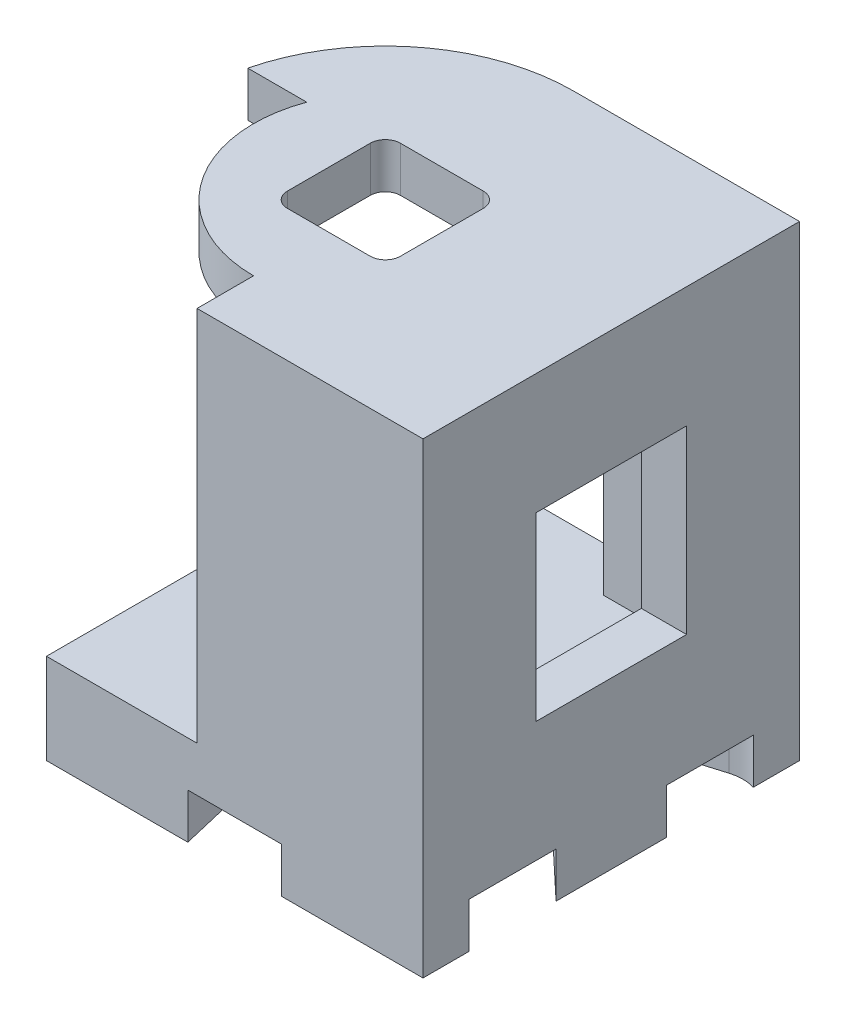
SolidWorks part; units mm, degrees
material "PBT General Purpose"
ref_plane "Front Plane" through (0, 0, 0) normal (0, 0, 1) x (1, 0, 0)
ref_plane "Top Plane" through (0, 0, 0) normal (0, 1, 0) x (1, 0, 0)
ref_plane "Right Plane" through (0, 0, 0) normal (1, 0, 0) x (0, 0, -1)
sketch "Sketch1" plane through (0, 0, 0) normal (0, 1, 0) x (1, 0, 0)
  line L1 (3.75, -3.75) -> (-3.75, -3.75)
  line L2 (3.75, -3.75) -> (3.75, 3.75)
  line L3 (3.75, 3.75) -> (-3.75, 3.75)
  line L4 (-3.75, -3.75) -> (-3.75, 3.75)
  line L5 (3.75, -3.75) -> (-3.75, 3.75) construction
  line L6 (3.75, 3.75) -> (-3.75, -3.75) construction
  line L7 (-15, -12.5) -> (15, -12.5)
  line L8 (-15, -12.5) -> (-15, 12.5)
  line L9 (-15, 12.5) -> (15, 12.5)
  line L10 (15, -12.5) -> (15, 12.5)
  line L11 (-15, -12.5) -> (15, 12.5) construction
  line L12 (-15, 12.5) -> (15, -12.5) construction
  point P0 (0, 0)
  dimension "D1" = 30
  dimension "D2" = 7.5
  dimension "D3" = 25
extrude "Boss-Extrude1" add sketch "Sketch1" along normal blind 3
fillet "Fillet1" radius 1 4 edges at (3.75, 1.5, 3.75) (3.75, 1.5, -3.75) (-3.75, 1.5, -3.75) (-3.75, 1.5, 3.75)
sketch "Sketch2" plane through (0, 0, 0) normal (0, -1, 0) x (-1, 0, 0)
  line L0 (8.2196, 3) -> (12.1347, 3)
  line L1 (0, -8.75) -> (0, -12.5)
  line L2 (-15, 12.5) -> (15, 12.5) construction
  line L3 (0, 12.5) -> (15, 12.5)
  line L4 (15, 12.5) -> (15, -12.5) construction
  line L5 (15, 12.5) -> (15, -12.5)
  line L6 (15, -12.5) -> (-15, -12.5) construction
  line L7 (15, -12.5) -> (0, -12.5)
  arc A0 (12.1347, 3) -> (0, 12.5) centre (0, 0) ccw
  arc A1 (0, -8.75) -> (8.2196, 3) centre (0, 0) ccw
  dimension "D2" = 2.8653
  dimension "D3" = 6.7804
extrude "Cut-Extrude1" cut sketch "Sketch2" against normal through all
sketch "Sketch3" plane through (0, 3, 0) normal (0, 1, 0) x (1, 0, 0)
  line L0 (15, 12.5) -> (0, 12.5) construction
  line L1 (15, -12.5) -> (13.2329, -12.5)
  line L2 (15, -12.5) -> (15, 12.5)
  line L3 (15, 12.5) -> (12, 12.5)
  line L4 (12, -9.5) -> (12, 12.5)
  line L6 (0, -12.5) -> (15, -12.5)
  line L7 (0, -12.5) -> (0, -9.5)
  line L8 (0, -9.5) -> (12, -9.5)
  line L9 (15, -12.5) -> (15, -9.999)
  line L10 (15, 12.5) -> (5, 12.5)
  line L11 (15, 12.5) -> (15, 9.5)
  line L12 (15, 9.5) -> (5, 9.5)
  line L13 (5, 12.5) -> (5, 9.5)
  line M8 (15, 12.5) -> (0, 12.5)
  line M12 (0, -8.75) -> (0, -12.5)
  line M13 (0, -12.5) -> (15, -12.5)
  line M14 (15, -12.5) -> (15, 12.5)
  dimension "D1" = 3
  dimension "D2" = 3
  dimension "D3" = 3
  dimension "D4" = 10
extrude "Boss-Extrude2" add sketch "Sketch3" against normal blind 31 contours L2 L12 L4 L8 M12 M13 M14 | L12 L4 M14 M8 | L13 L12 L4 M8 region at (14.1164, 3, 12.2337) region at (13.5, 3, -11) region at (8.5, 3, -11)
sketch "Sketch5" plane through (15, 0, 0) normal (1, 0, 0) x (0, 0, -1)
  line L0 (12.5, 3) -> (12.5, -28) construction
  line L1 (-12.5, -28) -> (12.5, -28)
  line L2 (-12.5, -28) -> (-12.5, -22)
  line L3 (-12.5, -22) -> (12.5, -22)
  line L4 (12.5, -28) -> (12.5, -22)
  dimension "D1" = 6
extrude "Boss-Extrude3" add sketch "Sketch5" against normal blind 25
sketch "Sketch6" plane through (0, -28, 0) normal (0, -1, 0) x (1, 0, 0)
  line L0 (-10, 12.5) -> (15, 12.5) construction
  line L1 (15, 12.5) -> (15, -12.5) construction
  line L2 (-0.225, 14.1436) -> (-2.073, 6.3188)
  line L3 (5.225, 14.1436) -> (7.073, 6.3188)
  arc A0 (-2.073, 6.3188) -> (7.073, 6.3188) centre (2.5, 0) ccw
  arc A1 (5.225, 14.1436) -> (-0.225, 14.1436) centre (2.5, 13.5) ccw
  point P8 (0, 0)
  point P13 (0, 0)
  dimension "D1" = 15.6
  dimension "D2" = 12.5
  dimension "D3" = 12.5
  dimension "D4" = 5.6
  dimension "D5" = 13.5
  dimension "D6" = 8.04
  dimension "D7" = 8.04
extrude "Cut-Extrude2" cut sketch "Sketch6" against normal blind 3
pattern_circular "CirPattern1" count 6 over 360 about axis through (2.5, -25, 0) along (0, -1, 0) of "Cut-Extrude2"
sketch "Sketch8" plane through (15, 0, 0) normal (1, 0, 0) x (0, 0, -1)
  line L0 (-12.5, 3) -> (-12.5, -28) construction
  line L1 (-5, -17) -> (5, -17)
  line L2 (-5, -17) -> (-5, -5)
  line L3 (-5, -5) -> (5, -5)
  line L4 (5, -17) -> (5, -5)
  line L5 (-5, -17) -> (5, -5) construction
  line L6 (-5, -5) -> (5, -17) construction
  line L7 (-12.5, 3) -> (12.5, 3) construction
  point P0 (0, -11)
  dimension "D1" = 10
  dimension "D2" = 12
  dimension "D3" = 7.5
  dimension "D4" = 8
extrude "Cut-Extrude3" cut sketch "Sketch8" against normal through all
sketch "Sketch9" plane through (0, -25, 0) normal (0, -1, 0) x (1, 0, 0)
  line L0 (5.6132, 12.5) -> (-0.6132, 12.5) construction
  line L1 (-10, 3.6651) -> (-10, -3.6651) construction
  circle A0 centre (2.5, 0) radius 5
  dimension "D1" = 10
  dimension "D2" = 12.5
  dimension "D3" = 12.5
